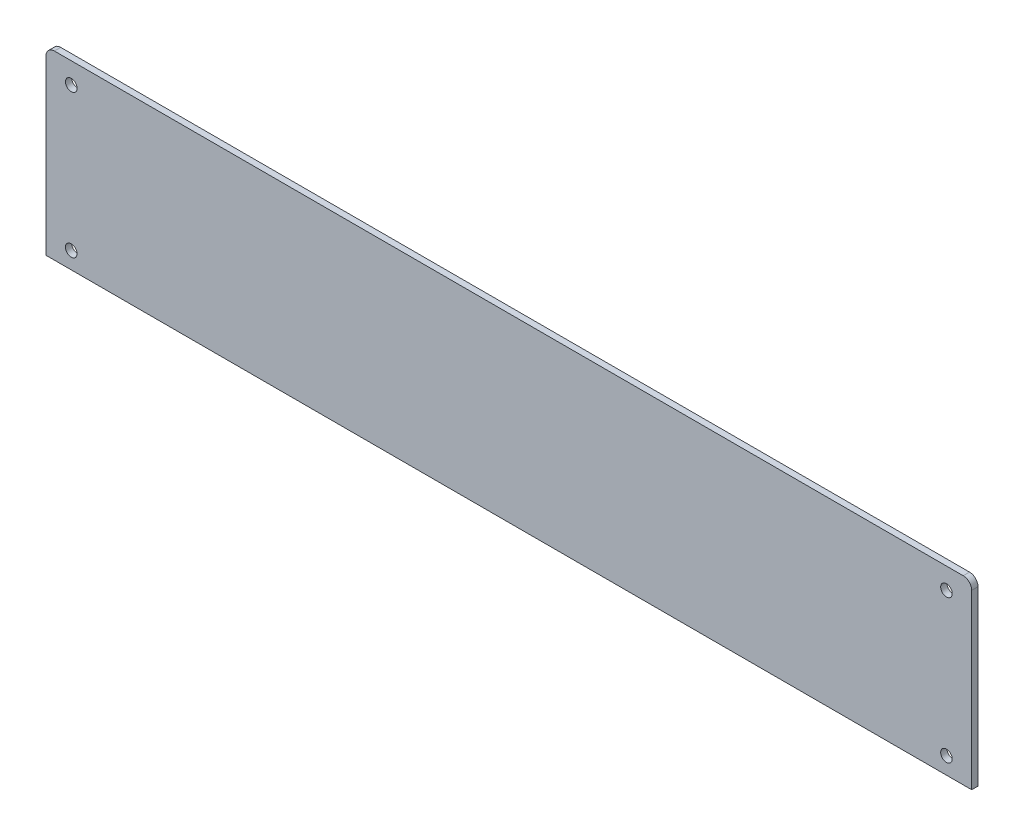
SolidWorks part; units mm, degrees
material "1060 Сплав"
ref_plane "Front" through (0, 0, 0) normal (0, 0, 1) x (1, 0, 0)
ref_plane "Top" through (0, 0, 0) normal (0, 1, 0) x (1, 0, 0)
ref_plane "Right" through (0, 0, 0) normal (1, 0, 0) x (0, 0, -1)
sketch "Эскиз1" plane through (0, 0, 0) normal (0, 0, 1) x (1, 0, 0)
  line L1 (0, 0) -> (440, 0)
  line L2 (0, 0) -> (0, 86.1)
  line L3 (0, 86.1) -> (440, 86.1)
  line L4 (440, 0) -> (440, 86.1)
  point P9 (440, 86.1)
  point P12 (0, 0)
  point P15 (0, 86.1)
  dimension "D1" = 86.1
  dimension "D2" = 440
extrude "Бобышка-Вытянуть1" add sketch "Эскиз1" along normal blind 3
sketch "Эскиз6" plane through (0, 0, 0) normal (0, 0, -1) x (-1, 0, 0)
  line L1 (-440, 0) -> (-440, 86.1) construction
  line L2 (0, 0) -> (-440, 0) construction
  line L5 (0, 86.1) -> (0, 0) construction
  circle A0 centre (-428, 76.1) radius 2.75
  circle A1 centre (-428, 8) radius 2.75
  circle A2 centre (-12, 8) radius 2.75
  circle A3 centre (-12, 76.1) radius 2.75
  dimension "D1" = 12
  dimension "D2" = 5.5
  dimension "D3" = 8
  dimension "D4" = 5.5
  dimension "D5" = 8
  dimension "D6" = 2
  dimension "D8" = 12
extrude "Вырез-Вытянуть1" cut sketch "Эскиз6" against normal through all
fillet "Скругление1" radius 4 2 edges at (0, 86.1, 1.5) (440, 86.1, 1.5)
